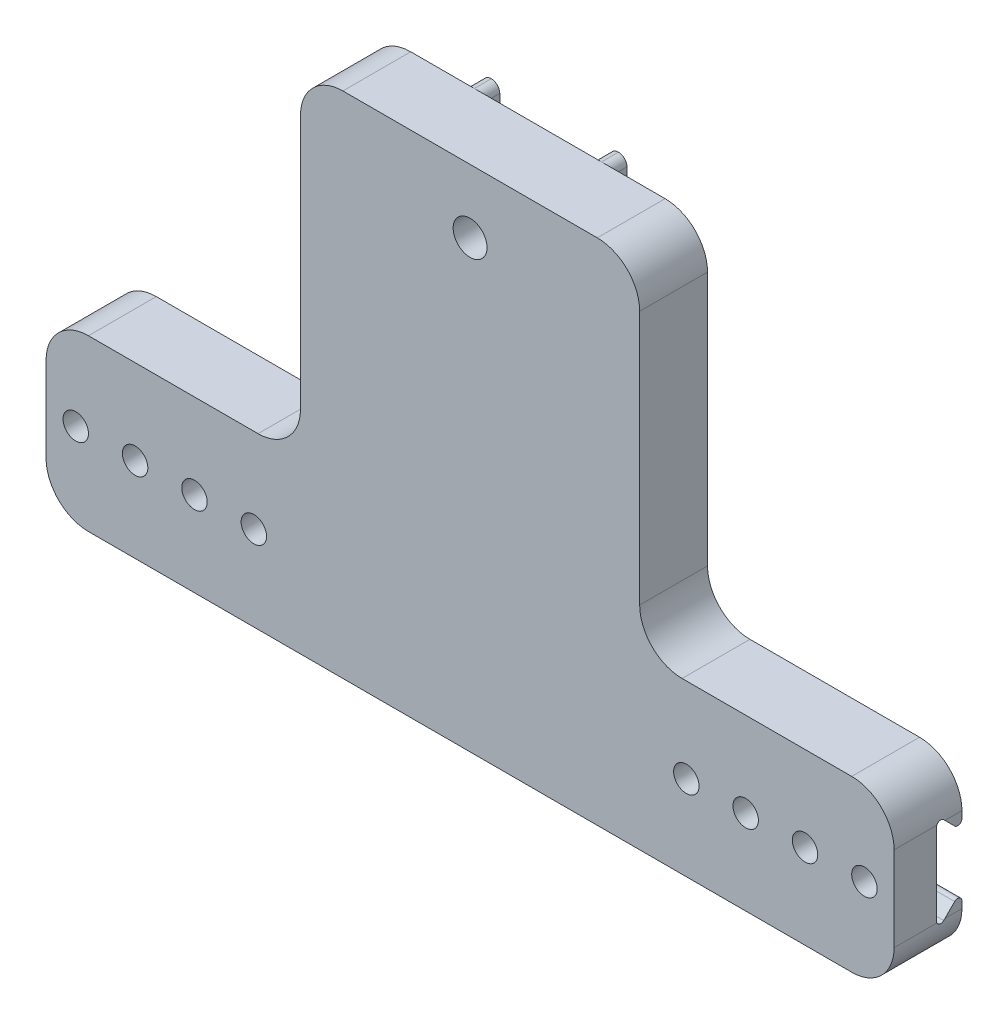
SolidWorks part; units mm, degrees
ref_plane "Front Plane" through (0, 0, 0) normal (0, 0, 1) x (1, 0, 0)
ref_plane "Top Plane" through (0, 0, 0) normal (0, 1, 0) x (1, 0, 0)
ref_plane "Right Plane" through (0, 0, 0) normal (1, 0, 0) x (0, 0, -1)
sketch "Sketch1" plane through (0, 0, 0) normal (0, 1, 0) x (1, 0, 0)
  line L1 (-20, 4) -> (20, 4)
  line L2 (-20, 4) -> (-20, -4)
  line L3 (-20, -4) -> (20, -4)
  line L4 (20, 4) -> (20, -4)
  line L5 (-20, 4) -> (20, -4) construction
  line L6 (-20, -4) -> (20, 4) construction
  point P0 (0, 0)
  dimension "D1" = 40
  dimension "D2" = 8
extrude "Boss-Extrude1" add sketch "Sketch1" against normal blind 60
sketch "Sketch2" plane through (20, 0, 0) normal (1, 0, 0) x (0, 0, -1)
  line L0 (-4, -60) -> (-4, 0) construction
  line L1 (4, -60) -> (-4, -60)
  line L2 (4, -60) -> (4, -40)
  line L3 (4, -40) -> (-4, -40)
  line L4 (-4, -60) -> (-4, -40)
  line L5 (0, -40) -> (0, -60) construction
  line L6 (4, -50) -> (-4, -50) construction
  point P532 (0, -50)
  dimension "D1" = 20
  dimension "D2" = 8
extrude "Boss-Extrude2" add sketch "Sketch2" along normal blind 30 contours L3 L4 L1 L2
sketch "Sketch3" plane through (50, 0, 0) normal (1, 0, 0) x (0, 0, -1)
  line L0 (1, -50) -> (1, -56)
  line L1 (1, -56) -> (4, -53)
  line L2 (4, -60) -> (4, -40) construction
  line L3 (1, -50) -> (1, -44)
  line L4 (1, -44) -> (4, -47)
  line L5 (4, -53) -> (4, -47)
  line L7 (4, -40) -> (-4, -40) construction
  dimension "D1" = 6
  dimension "D2" = 6
  dimension "D3" = 6
  dimension "D4" = 3
  dimension "D5" = 10
  dimension "D6" = 3
extrude "Cut-Extrude1" cut sketch "Sketch3" against normal blind 30 contours L0 L1 L5 L4 L3
sketch "Sketch6" plane through (0, 0, 4) normal (0, 0, 1) x (1, 0, 0)
  line L0 (50, -40) -> (20, -40) construction
  line L1 (50, -60) -> (50, -40) construction
  circle A0 centre (46.5, -50) radius 1.5
  point P4 (0, 0)
  point P5 (0, 0)
  point P8 (0, 0)
  dimension "D1" = 10
  dimension "D2" = 3
  dimension "D3" = 3.5
extrude "Cut-Extrude2" cut sketch "Sketch6" against normal through all contours A0
pattern_linear "LPattern1" count 4 spacing 7 along (-1, 0, 0) of "Cut-Extrude2"
mirror "Mirror3" about plane through (0, 0, 0) normal (1, 0, 0) of "LPattern1", "Cut-Extrude1", "Boss-Extrude2"
sketch "Sketch7" plane through (0, 0, 4) normal (0, 0, 1) x (1, 0, 0)
  circle A0 centre (0, -7.5) radius 2
  dimension "D1" = 7.5
extrude "Cut-Extrude3" cut sketch "Sketch7" against normal blind 30
sketch "Sketch8" plane through (0, 0, -4) normal (0, 0, -1) x (-1, 0, 0)
  line L0 (-20, 0) -> (20, 0) construction
  line L1 (-50, -60) -> (50, -60) construction
  line L2 (-8.5, 0) -> (-6.5, 0)
  line L3 (-8.5, 0) -> (-8.5, -60)
  line L4 (-8.5, -60) -> (-6.5, -60)
  line L5 (-6.5, 0) -> (-6.5, -60)
  line L6 (-7.5, -60) -> (-7.5, 0) construction
  line L7 (-8.5, -30) -> (-6.5, -30) construction
  line L9 (-20, -40) -> (-20, 0) construction
  point P662 (-7.5, -30)
  dimension "D1" = 2
  dimension "D2" = 12.5
extrude "Boss-Extrude3" add sketch "Sketch8" along normal blind 2
fillet "Fillet1" radius 1 2 edges at (8.5, 0, -5) (6.5, 0, -5)
mirror "Mirror4" about plane through (0, 0, 0) normal (1, 0, 0) of "Fillet1", "Boss-Extrude3"
fillet "Fillet2" radius 0.5 8 edges at (-35, -56, -1) (-35, -44, -1) (-35, -53, -4) (-35, -47, -4) (35, -44, -1) (35, -56, -1) (35, -53, -4) (35, -47, -4)
fillet "Fillet3" radius 5 8 edges at (-20, 0, 0) (20, 0, 0) (20, -40, 0) (-20, -40, 0) (-50, -60, 0) (-50, -40, 0) (50, -60, 0) (50, -40, 0)
